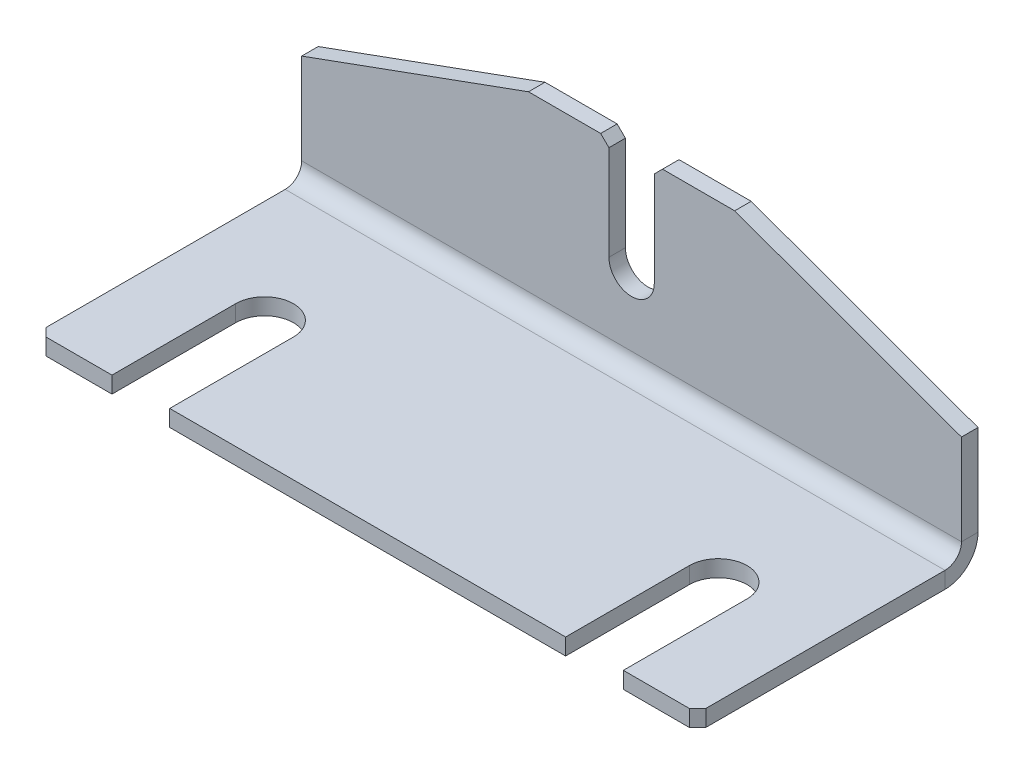
SolidWorks part; units mm, degrees
note: The reader was unsure of these and kept them because the rebuilt part matched: flange length of "Edge-Flange1".
material "AISI 1020"
ref_plane "Front Plane" through (0, 0, 0) normal (0, 0, 1) x (1, 0, 0)
ref_plane "Top Plane" through (0, 0, 0) normal (0, 1, 0) x (1, 0, 0)
ref_plane "Right Plane" through (0, 0, 0) normal (1, 0, 0) x (0, 0, -1)
sketch "Sketch1" plane through (0, 0, 0) normal (0, 1, 0) x (1, 0, 0)
  line L1 (0, 0) -> (18, 0)
  line L2 (0, 0) -> (0, 60)
  line L3 (0, 60) -> (160, 60)
  line L4 (160, 0) -> (160, 60)
  line L5 (142, 30) -> (142, 0)
  line L6 (128, 30) -> (128, 0)
  line L7 (80, 0) -> (80, 34.9331) construction
  line L9 (18, 30) -> (18, 0)
  line L10 (32, 30) -> (32, 0)
  line L11 (32, 0) -> (128, 0)
  line L12 (142, 0) -> (160, 0)
  arc A0 (142, 30) -> (128, 30) centre (135, 30) ccw
  arc A2 (18, 30) -> (32, 30) centre (25, 30) cw
  dimension "D5" = 7
  dimension "D3" = 25
  dimension "D7" = 25
  dimension "D8" = 7
  dimension "D1" = 60
  dimension "D2" = 160
  dimension "D4" = 14
  dimension "D6" = 14
  dimension "D9" = 30
base flange "Base-Flange1" sketch "Sketch1" thickness 4 reverse thickness direction no parameters "D1"=0.7366
edge flange "Edge-Flange1" sketch "Sketch8" flange angle 90 flange length 50 flange position bend outside bend radius 4 thickness 4 relief rectangular parameters "D6"=10
sketch "Sketch8" plane through (0, 0, -60) normal (0, 0, 1) x (1, 0, 0)
  line L2 (0, 0) -> (0, 26)
  line L3 (55, 46) -> (72.5, 46)
  line L4 (160, 26) -> (160, 0)
  line L5 (160, 0) -> (0, 0) construction
  line L6 (160, 0) -> (0, 0)
  line L7 (0, 26) -> (55, 46)
  line L8 (0, -4) -> (18, -4) construction
  line L9 (80, 0) -> (80, 73.5435) construction
  line L10 (160, 26) -> (105, 46)
  line L11 (74.5, 44) -> (74.5, 21)
  line L12 (85.5, 21) -> (85.5, 44)
  line L13 (87.5, 46) -> (105, 46)
  line L14 (72.5, 46) -> (74.5, 44)
  line L15 (85.5, 44) -> (87.5, 46)
  arc A0 (74.5, 21) -> (85.5, 21) centre (80, 21) ccw
  point P3 (74.5, 46)
  point P15 (85.5, 46)
  dimension "D3" = 5.5
  dimension "D4" = 25
  dimension "D1" = 55
  dimension "D2" = 30
  dimension "D5" = 20
  dimension "D6" = 2
  dimension "D7" = 45
  dimension "D8" = 2
  dimension "D9" = 45
bend "EdgeBend1" bend radius 4 bend angle 90 parameters "D5"=1
chamfer "Chamfer1" distance 2 angle 45 2 edges at (0, -2, 0) (160, -2, 0)
ref_plane "Plane1" through (80, 0, 0) normal (1, 0, 0) x (0, 0, -1)
sketch "Bend-Lines1" [suppressed] plane through (0, 0, 0) normal (0, 1, 0) x (1, 0, 0)
sketch "Bounding-Box1" [suppressed] plane through (0, 0, 0) normal (0, 1, 0) x (1, 0, 0)
sheet metal parameters "Sheet-Metal1" thickness 4 parameters "D1"=0.7366
flat pattern "Flat-Pattern1" [suppressed]
sketch "Bend-Lines2" plane through (0, 0, 0) normal (0, 1, 0) x (1, 0, 0)
sketch3d "Bounding-Box2" [suppressed]
  line L0 (-25, -30, 0) -> (135, -30, 0) construction
  line L1 (-25, 30, 0) -> (135, 30, 0) construction
  line L2 (-25, -30, 0) -> (-25, 30, 0) construction
  line L3 (135, -30, 0) -> (135, 30, 0) construction
sheet metal parameters "Sheet-Metal2" thickness 4 parameters "D1"=0.7366
flat pattern "Flat-Pattern1"
sketch "Bend-Lines2" plane through (0, 0, 0) normal (0, 1, 0) x (1, 0, 0)
  line L0 (160, 64.7124) -> (0, 64.7124) construction
  line L1 (160, 64.7124) -> (0, 64.7124) construction
sketch3d "Bounding-Box2" [suppressed]
  line L0 (25, -30, 0) -> (-135, -30, 0) construction
  line L1 (25, 81.4248, 0) -> (-135, 81.4248, 0) construction
  line L2 (25, -30, 0) -> (25, 81.4248, 0) construction
  line L3 (-135, -30, 0) -> (-135, 81.4248, 0) construction
bend of the flat pattern "Flatten-<EdgeBend1>1"
